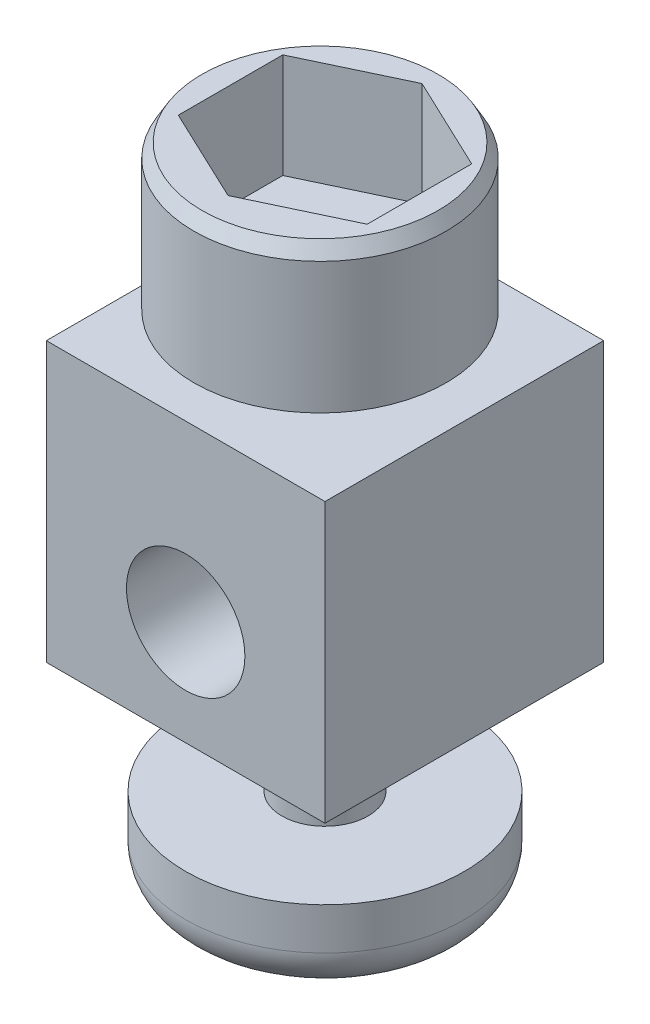
SolidWorks part; units mm, degrees
note: '?' marks a value the reader was unsure of.
ref_plane "Front Plane" through (0, 0, 0) normal (0, 0, 1) x (1, 0, 0)
ref_plane "Top Plane" through (0, 0, 0) normal (0, 1, 0) x (1, 0, 0)
ref_plane "Right Plane" through (0, 0, 0) normal (1, 0, 0) x (0, 0, -1)
sketch "Sketch1" plane through (0, 0, 0) normal (0, 0, 1) x (1, 0, 0)
  line L0 (-2.54, 2.54) -> (-2.54, -2.54)
  line L1 (2.54, -2.54) -> (2.54, 2.54)
  line L2 (2.54, 2.54) -> (-2.54, 2.54)
  line L3 (-2.54, -2.54) -> (2.54, -2.54)
  dimension "D1" = 2.54
  dimension "D2" = 5.08
  dimension "D3" = 5.08
  dimension "D4" = 2.54
extrude "Extrude1" add sketch "Sketch1" along normal blind 5.08
sketch "Sketch2" plane through (0, 0, 5.08) normal (0, 0, 1) x (1, 0, 0)
  circle A0 centre (0, -0.635) radius 1.0795
  dimension "D1" = 2.159
extrude "Cut-Extrude1" cut sketch "Sketch2" against normal through all
sketch "Sketch3" plane through (0, -2.54, 0) normal (0, -1, 0) x (1, 0, 0)
  line L0 (-2.54, 5.08) -> (-2.54, 0) construction
  circle A0 centre (0, 2.54) radius 0.7874
  point P2 (-2.54, 2.54)
  dimension "D1" = 1.5748
  dimension "D2" = 2.54
  dimension "D3" = 2.54
extrude "Extrude2" add sketch "Sketch3" along normal blind 4.0132
sketch "Sketch4" plane through (0, 2.54, 0) normal (0, 1, 0) x (-1, 0, 0)
  circle A0 centre (0, 2.6302) radius 1.3716
  dimension "D1" = 2.7432
extrude "Extrude3" add sketch "Sketch4" along normal blind 3.175
sketch "Sketch5" plane through (0, 5.715, 0) normal (0, 1, 0) x (-1, 0, 0)
  circle A0 centre (0, 2.6302) radius 2.2987
  circle A1 centre (0, 2.6302) radius 1.3716 construction
  dimension "D1" = 4.5974
extrude "Extrude4" add sketch "Sketch5" against normal blind 2.794
chamfer "Chamfer1" distance 0.254 angle 30 1 edges at (0, 5.715, 4.9289)
sketch "Sketch6" plane through (0, 5.715, 0) normal (0, 1, 0) x (-1, 0, 0)
  line L0 (0, 0) -> (0, 5.08) construction
  line L1 (-2.54, 5.08) -> (2.54, 5.08) construction
  line L2 (-2.54, 0) -> (-2.54, 2.54) construction
  line L3 (-2.54, 5.08) -> (-2.54, 0) construction
  line L4 (-2.54, 2.54) -> (2.54, 2.54) construction
  line L5 (2.54, 5.08) -> (2.54, 0) construction
  line L6 (-1.7216, 1.5875) -> (-1.7216, 3.4925)
  line L7 (0, 0.772) -> (-1.7216, 1.5875)
  line L8 (0, 4.308) -> (-1.7216, 3.4925)
  line L9 (1.7215, 1.5878) -> (0, 0.772)
  line L10 (1.7215, 1.5878) -> (1.7218, 3.4928)
  line L11 (1.7218, 3.4928) -> (0, 4.308)
  line L12 (-1.7216, 1.5875) -> (1.7218, 3.4928) construction
  line L13 (1.7215, 1.5878) -> (-1.7216, 3.4925) construction
  dimension "D1" = 1.905
  dimension "D2" = 0.9525
  dimension "D3" = 1.905
  dimension "D4" = 1.905
  dimension "D5" = 1.905
  dimension "D6" = 1.905
  dimension "D7" = 1.905
extrude "Cut-Extrude2" cut sketch "Sketch6" against normal blind 1.905 contours L7 L6 L8 L11 L10 L9
chamfer "Chamfer2" distance 0.254 angle 30 1 edges at (0, 2.921, 4.9289)
ref_axis "Axis1" through (0, -2.54, 2.54) along (0, -1, 0)?
sketch "Sketch9" plane through (-1.1933, 0, 0.8353) normal (-0.8192, 0, 0.5735) x (0.5735, 0, 0.8192)
  line L0 (2.8682, -6.5532) -> (2.8682, -2.54) construction
  line L3 (2.0808, -4.5714) -> (-0.4592, -4.5714)
  line L4 (2.0808, -4.5714) -> (2.0808, -6.0954)
  line L5 (2.0808, -6.0954) -> (0.3028, -6.0954)
  line L6 (-0.4592, -4.5714) -> (-0.4592, -5.3334)
  arc A0 (-0.4592, -5.3334) -> (0.3028, -6.0954) centre (0.3028, -5.3334) ccw
  dimension "D4" = 1.524
  dimension "D1" = 0.7874
  dimension "D2" = 2.54
revolve "Revolve1" add sketch "Sketch9" angle 360 about L4
